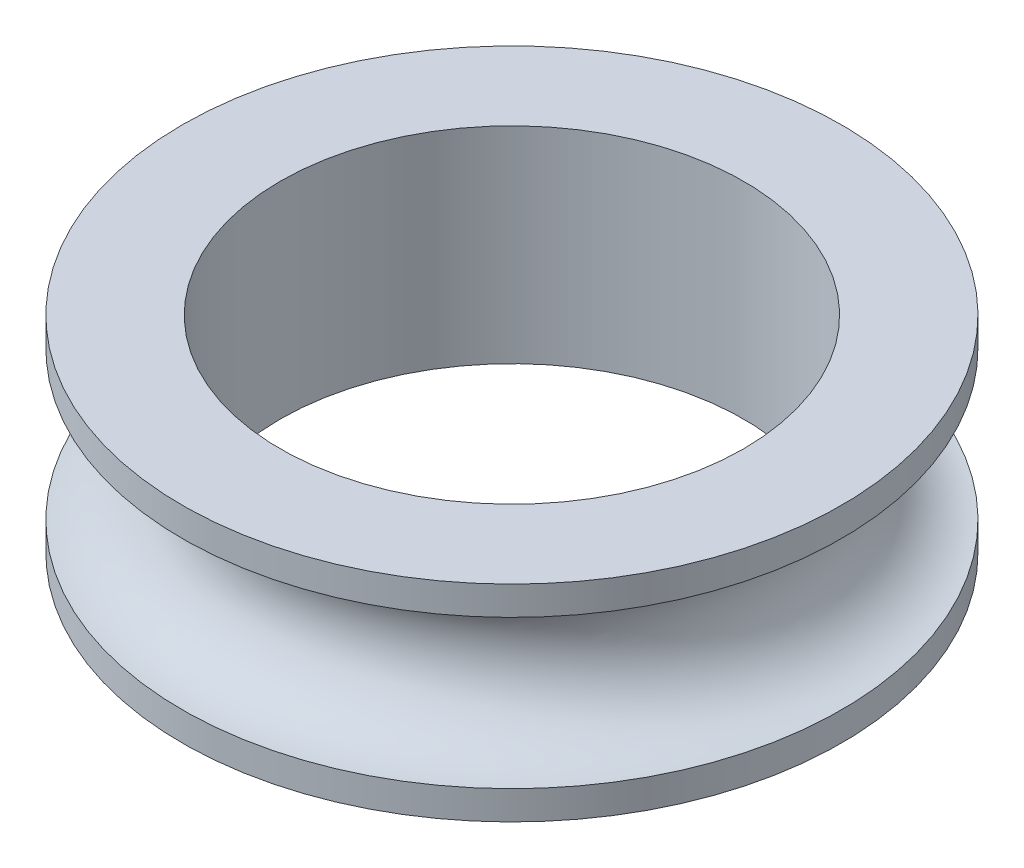
SolidWorks part; units mm, degrees
ref_plane "Front Plane" through (0, 0, 0) normal (0, 0, 1) x (1, 0, 0)
ref_plane "Top Plane" through (0, 0, 0) normal (0, 1, 0) x (1, 0, 0)
ref_plane "Right Plane" through (0, 0, 0) normal (1, 0, 0) x (0, 0, -1)
sketch "Sketch1" plane through (0, 0, 0) normal (0, 0, 1) x (1, 0, 0)
  line L0 (-8, -1.8) -> (-8, -2.5)
  line L1 (0, 2.5) -> (-8, 2.5)
  line L2 (0, 2.5) -> (0, -2.5)
  line L3 (0, -2.5) -> (-8, -2.5)
  line L4 (-8, 2.5) -> (-8, 1.8)
  arc A0 (-8, -1.8) -> (-8, 1.8) centre (-8, 0) ccw
  point P4 (0, 0)
  dimension "D2" = 1.8
  dimension "D1" = 5
  dimension "D3" = 0.7
  dimension "D4" = 8
ref_axis "Axis1" through (0, 2.5, 0) along (0, -1, 0)
revolve "Revolve1" add sketch "Sketch1" angle 360 about L2
sketch "Sketch2" plane through (0, 2.5, 0) normal (0, 1, 0) x (1, 0, 0)
  circle A0 centre (0, 0) radius 5.625
  dimension "D1" = 11.25
extrude "Cut-Extrude1" cut sketch "Sketch2" against normal through all
